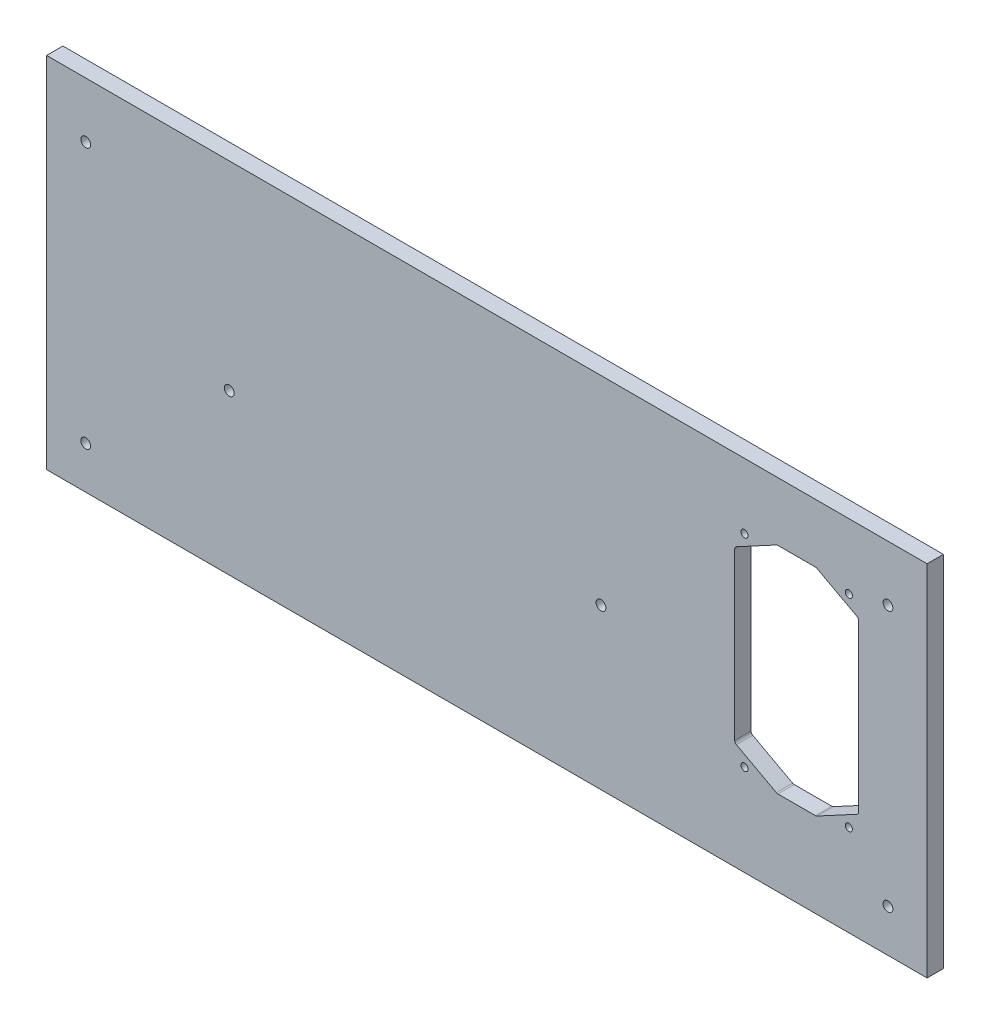
SolidWorks part; units mm, degrees
material "Acrylic (Medium-high impact)"
ref_plane "Front Plane" through (0, 0, 0) normal (0, 0, 1) x (1, 0, 0)
ref_plane "Top Plane" through (0, 0, 0) normal (0, 1, 0) x (1, 0, 0)
ref_plane "Right Plane" through (0, 0, 0) normal (1, 0, 0) x (0, 0, -1)
sketch "Sketch1" plane through (0, 0, 0) normal (0, 0, 1) x (1, 0, 0)
  line L1 (135, -55) -> (-135, -55)
  line L2 (135, -55) -> (135, 55)
  line L3 (135, 55) -> (-135, 55)
  line L4 (-135, -55) -> (-135, 55)
  line L5 (135, -55) -> (-135, 55) construction
  line L6 (135, 55) -> (-135, -55) construction
  point P0 (0, 0)
  dimension "D1" = 110
  dimension "D2" = 270
extrude "Base" add sketch "Sketch1" along normal mid plane 5
sketch "Sketch2" plane through (0, 0, 2.5) normal (0, 0, 1) x (1, 0, 0)
  line L0 (135, -55) -> (135, 55) construction
  line L1 (-135, -55) -> (135, -55) construction
  line L2 (-135, 55) -> (-135, -55) construction
  line L3 (135, 55) -> (-135, 55) construction
  circle A0 centre (-123, -42) radius 1.5
  circle A2 centre (123, -42) radius 1.5
  circle A3 centre (123, 38) radius 1.5
  circle A4 centre (-123, 38) radius 1.5
  dimension "D1" = 12
  dimension "D5" = 3
  dimension "D2" = 13
  dimension "D4" = 12
  dimension "D6" = 17
extrude "MountHoles" cut sketch "Sketch2" against normal through all
sketch "Sketch3" plane through (0, 0, -2.5) normal (0, 0, -1) x (-1, 0, 0)
  line L0 (-135, -55) -> (-135, 55) construction
  line L1 (135, -55) -> (-135, -55) construction
  circle A0 centre (-35, -6) radius 1.5
  circle A1 centre (79, -6) radius 1.5
  dimension "D4" = 3
  dimension "D1" = 114
  dimension "D2" = 100
  dimension "D3" = 49
extrude "MiddlePartHoles" cut sketch "Sketch3" against normal through all
chamfer "ChamferAll" distance 1.7 angle 45 6 edges at (-121.5, -42, -2.5) (124.5, -42, -2.5) (-121.5, 38, -2.5) (124.5, 38, -2.5) (-80.5, -6, -2.5) (33.5, -6, -2.5)
sketch "Sketch4" plane through (0, 0, -2.5) normal (0, 0, -1) x (-1, 0, 0)
  line L0 (-101, 37) -> (-114, 30)
  line L1 (-89, -29) -> (-101, -29)
  line L2 (-76, -22) -> (-76, 30)
  line L3 (-89, 37) -> (-101, 37)
  line L4 (-114, -22) -> (-114, 30)
  line L5 (-76, -29) -> (-114, 37) construction
  line L6 (-76, 37) -> (-114, -29) construction
  line L7 (-79, -27) -> (-111, -27) construction
  line L8 (-79, -27) -> (-79, 35) construction
  line L9 (-79, 35) -> (-111, 35) construction
  line L10 (-111, -27) -> (-111, 35) construction
  line L11 (-79, -27) -> (-111, 35) construction
  line L12 (-79, 35) -> (-111, -27) construction
  line L13 (-101, -29) -> (-114, -22)
  line L14 (-95, 4) -> (-95, 17.8562) construction
  line L15 (-76, 30) -> (-89, 37)
  line L16 (-76, -22) -> (-89, -29)
  line L17 (-135, -55) -> (-135, 55) construction
  line L18 (135, -55) -> (-135, -55) construction
  circle A0 centre (-79, 35) radius 1.1
  circle A1 centre (-111, 35) radius 1.1
  circle A2 centre (-111, -27) radius 1.1
  circle A3 centre (-79, -27) radius 1.1
  point P0 (-95, 4)
  point P14 (-95, 4)
  dimension "D1" = 2.2
  dimension "D2" = 62
  dimension "D3" = 32
  dimension "D4" = 38
  dimension "D5" = 66
  dimension "D6" = 13
  dimension "D7" = 7
  dimension "D8" = 13
  dimension "D9" = 7
  dimension "D10" = 7
  dimension "D11" = 13
  dimension "D12" = 13
  dimension "D13" = 7
  dimension "D14" = 40
  dimension "D15" = 59
extrude "Cut-Extrude1" cut sketch "Sketch4" against normal through all
fillet "Fillet1" radius 1 8 edges at (76, 30, 0) (89, -29, 0) (101, -29, 0) (114, -22, 0) (114, 30, 0) (101, 37, 0) (89, 37, 0) (76, -22, 0)
